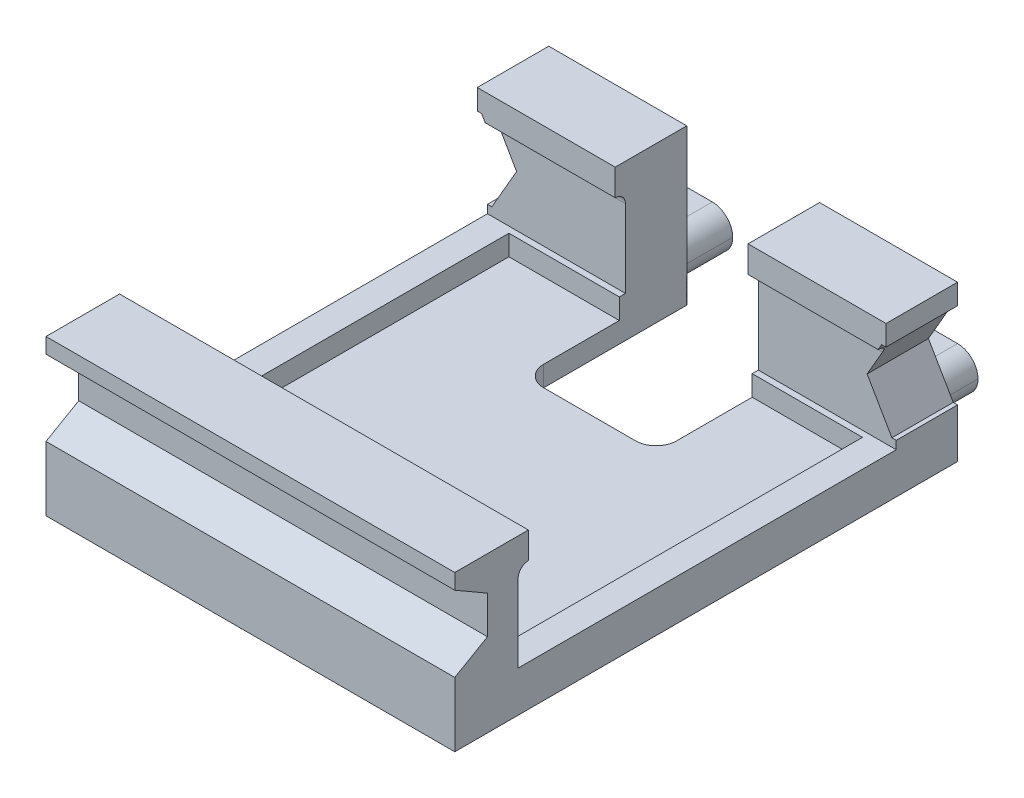
SolidWorks part; units mm, degrees
ref_plane "Front Plane" through (0, 0, 0) normal (0, 0, 1) x (1, 0, 0)
ref_plane "Top Plane" through (0, 0, 0) normal (0, 1, 0) x (1, 0, 0)
ref_plane "Right Plane" through (0, 0, 0) normal (1, 0, 0) x (0, 0, -1)
sketch "Sketch1" plane through (0, 0, 0) normal (0, 1, 0) x (1, 0, 0)
  line L0 (0, 11.5) -> (0, -11.5) construction
  line L1 (10, 11.5) -> (-10, 11.5)
  line L2 (10, 11.5) -> (10, -11.5)
  line L3 (10, -11.5) -> (-10, -11.5)
  line L4 (-10, 11.5) -> (-10, -11.5)
  line L5 (10, 11.5) -> (-10, -11.5) construction
  line L6 (10, -11.5) -> (-10, 11.5) construction
  line L21 (-3.25, 3.5) -> (3.25, 3.5)
  line L29 (-3.25, 3.5) -> (-3.25, 11.5)
  line L30 (-3.25, 11.5) -> (3.25, 11.5)
  line L31 (3.25, 3.5) -> (3.25, 11.5)
  line L32 (-3.25, 3.5) -> (3.25, 11.5) construction
  line L33 (-3.25, 11.5) -> (3.25, 3.5) construction
  line L41 (-6, 14.5) -> (-6, 11.5) construction
  line L42 (-4, 11.5) -> (-8, 11.5)
  line L43 (-4, 11.5) -> (-4, 14.5)
  line L44 (-4, 14.5) -> (-8, 14.5)
  line L45 (-8, 11.5) -> (-8, 14.5)
  line L46 (4, 11.5) -> (8, 11.5)
  line L47 (8, 11.5) -> (8, 14.5)
  line L48 (4, 14.5) -> (8, 14.5)
  line L49 (4, 11.5) -> (4, 14.5)
  point P0 (0, 0)
  point P14 (0, 7.5)
  dimension "D1" = 20
  dimension "D2" = 23
  dimension "D3" = 4
  dimension "D6" = 6.5
  dimension "D7" = 8
  dimension "D8" = 12
  dimension "D9" = 3
extrude "Boss-Extrude1" add sketch "Sketch1" along normal blind 2 contours L4 | L1 L4 L3 L2 | L2 | L31 L21 L29 L1 | L43 L1 | L1 region at (0, 0, 0.9559) region at (6, 0, -13) region at (-6, 0, -13)
fillet "Fillet1" radius 1 10 edges at (-3.25, 1, -3.5) (3.25, 1, -3.5) (-8, 0, -13) (-8, 2, -13) (4, 0, -13) (4, 2, -13) (8, 0, -13) (8, 2, -13) (-4, 0, -13) (-4, 2, -13)
sketch "Sketch4" plane through (0, 2, 0) normal (0, 1, 0) x (1, 0, 0)
  line L0 (0, 5.3573) -> (0, -4.2859) construction
  line L2 (-8.65, 8.2) -> (8.65, 8.2)
  line L3 (-8.65, 8.2) -> (-8.65, -9.5)
  line L4 (-8.65, -9.5) -> (8.65, -9.5)
  line L5 (8.65, 8.2) -> (8.65, -9.5)
  line L6 (-8.65, 8.2) -> (8.65, -9.5) construction
  line L7 (-8.65, -9.5) -> (8.65, 8.2) construction
  line L11 (10, -11.5) -> (-10, -11.5) construction
  point P1 (0, -0.65)
  dimension "D1" = 17.3
  dimension "D2" = 2
  dimension "D3" = 17.7
extrude "Cut-Extrude3" cut sketch "Sketch4" against normal blind 1
sketch "Sketch5" plane through (10, 0, 0) normal (1, 0, 0) x (0, 0, -1)
  line L0 (8.2, 1) -> (-9.5, 1) construction
  line L1 (8.2, 1) -> (-9.5, 1)
  line L2 (11.5, 2) -> (-11.5, 2) construction
  line L3 (-11.5, 2) -> (-10, 2)
  line L4 (-11.5, 2) -> (-11.5, 6.3)
  line L5 (-11.5, 6.3) -> (-10, 6.3)
  line L6 (-10, 2) -> (-10, 6.3)
  line L7 (11.5, 2) -> (8.5, 2)
  line L8 (11.5, 2) -> (11.5, 6.3)
  line L9 (11.5, 6.3) -> (8.5, 6.3)
  line L10 (8.5, 2) -> (8.5, 6.3)
  line L11 (-11.5, 6.3) -> (-9.5, 6.3)
  line L12 (-11.5, 6.3) -> (-11.5, 7.6)
  line L13 (-11.5, 7.6) -> (-9.5, 7.6)
  line L14 (-9.5, 6.3) -> (-9.5, 7.6)
  line L15 (11.5, 6.3) -> (8, 6.3)
  line L16 (11.5, 6.3) -> (11.5, 7.6)
  line L17 (11.5, 7.6) -> (8, 7.6)
  line L18 (8, 6.3) -> (8, 7.6)
  line L19 (-11.5, 2) -> (-11.5, 0) construction
  line L20 (11.5, 2) -> (11.5, 0) construction
  point P22 (0, 0)
  dimension "D1" = 1.5
  dimension "D2" = 5.3
  dimension "D3" = 18.5
  dimension "D4" = 1.3
  dimension "D5" = 0.5
  dimension "D6" = 0.5
extrude "Boss-Extrude3" add sketch "Sketch5" against normal up to surface (20 mm away) contours L6 L5 L4 | L11 L14 L13 L12 L5 | L18 L15 L9 L16 L17 | L10 L7 L8 L9 region at (10, 4.15, 10.75) region at (10, 6.95, 10.5) region at (10, 4.15, -10) region at (10, 6.95, -9.75) up to face at (-10, 1, 0)
sketch "Sketch7" plane through (0, 7.6, 0) normal (0, 1, 0) x (1, 0, 0)
  line L1 (-3.25, 11.5) -> (3.25, 11.5)
  line L2 (-3.25, 11.5) -> (-3.25, 8)
  line L3 (-3.25, 8) -> (3.25, 8)
  line L4 (3.25, 11.5) -> (3.25, 8)
  line L5 (-10, 8) -> (10, 8) construction
  line L11 (0, 5.6258) -> (0, -4.3103) construction
  line L16 (3.25, 4.5) -> (3.25, 8.2) construction
  line L17 (-10, 8) -> (10, 8) construction
  point P5 (3.25, 8)
extrude "Cut-Extrude5" cut sketch "Sketch7" against normal up to next
sketch "Sketch8" plane through (0, 0, -11.5) normal (0, 0, -1) x (-1, 0, 0)
  line L0 (-3.25, 7.6) -> (-10, 7.6) construction
  line L1 (-8.5751, 4.5) -> (-9.7876, 6.6)
  line L2 (-9.7876, 6.6) -> (-12.2124, 6.6)
  line L3 (-12.2124, 6.6) -> (-13.4249, 4.5)
  line L4 (-13.4249, 4.5) -> (-12.2124, 2.4)
  line L5 (-12.2124, 2.4) -> (-9.7876, 2.4)
  line L6 (-9.7876, 2.4) -> (-8.5751, 4.5)
  line L7 (0, 12.0608) -> (0, -4.099) construction
  line L8 (12.2124, 2.4) -> (9.7876, 2.4)
  line L9 (13.4249, 4.5) -> (12.2124, 2.4)
  line L10 (12.2124, 6.6) -> (13.4249, 4.5)
  line L11 (9.7876, 6.6) -> (12.2124, 6.6)
  line L12 (8.5751, 4.5) -> (9.7876, 6.6)
  line L13 (9.7876, 2.4) -> (8.5751, 4.5)
  circle A0 centre (-11, 4.5) radius 2.1 construction
  dimension "D1" = 3.1
  dimension "D2" = 22
  dimension "D3" = 4.2
extrude "Cut-Extrude6" cut sketch "Sketch8" against normal blind 3.5
fillet "Fillet3" radius 0.5 3 edges at (6.4322, 6.3, -8.5) (-6.4322, 6.3, -8.5) (0, 6.3, 10)
sketch "Sketch9" plane through (10, 0, 0) normal (1, 0, 0) x (0, 0, -1)
  line L0 (-11.5, 7.6) -> (-11.5, 0) construction
  line L1 (-11.5, 4.0762) -> (-11.5, 5.9238)
  line L2 (-11.5, 5.9238) -> (-13.1, 6.8475)
  line L3 (-13.1, 6.8475) -> (-14.7, 5.9238)
  line L4 (-14.7, 5.9238) -> (-14.7, 4.0762)
  line L5 (-14.7, 4.0762) -> (-13.1, 3.1525)
  line L6 (-13.1, 3.1525) -> (-11.5, 4.0762)
  line L7 (-11.5, 7.6) -> (-9.5, 7.6) construction
  line L8 (-13.1, 6.8475) -> (-13.1, 7.6)
  line L9 (-13.1, 7.6) -> (-11.5, 7.6)
  line L10 (-13.1, 3.1525) -> (-13.1, 0)
  line L11 (-13.1, 0) -> (-11.5, 0)
  circle A0 centre (-13.1, 5) radius 1.6 construction
  line M11 (-11.5, 7.6) -> (-11.5, 0)
  dimension "D1" = 3.2
  dimension "D2" = 2.6
extrude "Boss-Extrude4" add sketch "Sketch9" against normal up to surface (20 mm away) contours L9 L8 L2 M11 | L10 L11 L6 M11 region at (10, 1.817, 12.2659) region at (10, 6.9635, 12.1986) up to face at (-10, 3.6204, 2.2104)
